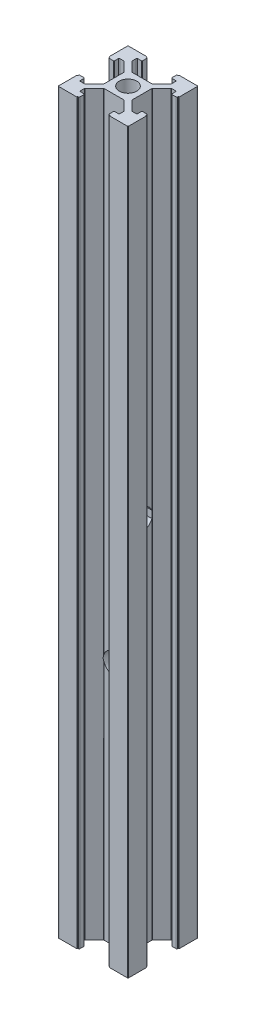
SolidWorks part; units mm, degrees
material "6063-O"
ref_plane "Ön Düzlem" through (0, 0, 0) normal (0, 0, 1) x (1, 0, 0)
ref_plane "Üst Düzlem" through (0, 0, 0) normal (0, 1, 0) x (1, 0, 0)
ref_plane "Sağ Düzlem" through (0, 0, 0) normal (1, 0, 0) x (0, 0, -1)
sketch "Sketch1" plane through (0, 0, 0) normal (0, 1, 0) x (1, 0, 0)
  line L0 (-10, 4.65) -> (-9.8, 4.65)
  line L1 (-9.8, -10) -> (-4.65, -10)
  line L2 (-10, -9.8) -> (-10, -4.65)
  line L3 (-9.8, 10) -> (-4.65, 10)
  line L4 (10, -9.8) -> (10, -4.65)
  line L5 (-10, -10) -> (10, 10) construction
  line L6 (-10, 10) -> (10, -10) construction
  line L7 (-9.8, 4.65) -> (-9.8, 4.4)
  line L8 (-9.6, 4.2) -> (-8.4, 4.2)
  line L9 (-4, 2.8172) -> (-4, -2.8172)
  line L10 (-8.2, 4.4) -> (-8.2, 5.45)
  line L11 (-8, 5.65) -> (-6.8328, 5.65)
  line L12 (-6.6914, 5.5914) -> (-4.0586, 2.9586)
  line L13 (-9.8, -4.65) -> (-10, -4.65)
  line L14 (-6.6914, -5.5914) -> (-4.0586, -2.9586)
  line L15 (-8, -5.65) -> (-6.8328, -5.65)
  line L16 (-8.2, -4.4) -> (-8.2, -5.45)
  line L17 (-9.6, -4.2) -> (-8.4, -4.2)
  line L18 (-9.8, -4.65) -> (-9.8, -4.4)
  line L19 (4.65, 10) -> (4.65, 9.8)
  line L20 (-10, 4.65) -> (-10, 9.8)
  line L21 (4.65, 9.8) -> (4.4, 9.8)
  line L22 (4.2, 9.6) -> (4.2, 8.4)
  line L23 (4.4, 8.2) -> (5.45, 8.2)
  line L24 (5.65, 8) -> (5.65, 6.8328)
  line L25 (5.5914, 6.6914) -> (2.9586, 4.0586)
  line L26 (2.8172, 4) -> (-2.8172, 4)
  line L27 (-5.5914, 6.6914) -> (-2.9586, 4.0586)
  line L28 (-5.65, 8) -> (-5.65, 6.8328)
  line L29 (-4.4, 8.2) -> (-5.45, 8.2)
  line L30 (-4.2, 9.6) -> (-4.2, 8.4)
  line L31 (-4.65, 9.8) -> (-4.4, 9.8)
  line L32 (-4.65, 9.8) -> (-4.65, 10)
  line L33 (10, -4.65) -> (9.8, -4.65)
  line L34 (9.8, -4.65) -> (9.8, -4.4)
  line L35 (9.6, -4.2) -> (8.4, -4.2)
  line L36 (8.2, -4.4) -> (8.2, -5.45)
  line L37 (8, -5.65) -> (6.8328, -5.65)
  line L38 (6.6914, -5.5914) -> (4.0586, -2.9586)
  line L39 (4, -2.8172) -> (4, 2.8172)
  line L40 (6.6914, 5.5914) -> (4.0586, 2.9586)
  line L41 (8, 5.65) -> (6.8328, 5.65)
  line L42 (8.2, 4.4) -> (8.2, 5.45)
  line L43 (9.6, 4.2) -> (8.4, 4.2)
  line L44 (9.8, 4.65) -> (9.8, 4.4)
  line L45 (9.8, 4.65) -> (10, 4.65)
  line L46 (-4.65, -10) -> (-4.65, -9.8)
  line L47 (-4.65, -9.8) -> (-4.4, -9.8)
  line L48 (-4.2, -9.6) -> (-4.2, -8.4)
  line L49 (-4.4, -8.2) -> (-5.45, -8.2)
  line L50 (-5.65, -8) -> (-5.65, -6.8328)
  line L51 (-5.5914, -6.6914) -> (-2.9586, -4.0586)
  line L52 (-2.8172, -4) -> (2.8172, -4)
  line L53 (5.5914, -6.6914) -> (2.9586, -4.0586)
  line L54 (5.65, -8) -> (5.65, -6.8328)
  line L55 (4.4, -8.2) -> (5.45, -8.2)
  line L56 (4.2, -9.6) -> (4.2, -8.4)
  line L57 (4.65, -9.8) -> (4.4, -9.8)
  line L58 (4.65, -9.8) -> (4.65, -10)
  line L59 (4.65, -10) -> (9.8, -10)
  line L60 (10, 4.65) -> (10, 9.8)
  line L61 (4.65, 10) -> (9.8, 10)
  arc A0 (-9.8, 4.4) -> (-9.6, 4.2) centre (-9.6, 4.4) ccw
  arc A1 (-9.8, -4.4) -> (-9.6, -4.2) centre (-9.6, -4.4) cw
  arc A2 (-8.4, 4.2) -> (-8.2, 4.4) centre (-8.4, 4.4) ccw
  arc A3 (-8.2, 5.45) -> (-8, 5.65) centre (-8, 5.45) cw
  arc A4 (-6.6914, 5.5914) -> (-6.8328, 5.65) centre (-6.8328, 5.45) ccw
  arc A5 (-4, 2.8172) -> (-4.0586, 2.9586) centre (-4.2, 2.8172) ccw
  arc A6 (-6.6914, -5.5914) -> (-6.8328, -5.65) centre (-6.8328, -5.45) cw
  arc A7 (-4, -2.8172) -> (-4.0586, -2.9586) centre (-4.2, -2.8172) cw
  arc A8 (-8, -5.65) -> (-8.2, -5.45) centre (-8, -5.45) cw
  arc A9 (-8.2, -4.4) -> (-8.4, -4.2) centre (-8.4, -4.4) ccw
  arc A10 (4.4, 9.8) -> (4.2, 9.6) centre (4.4, 9.6) ccw
  arc A11 (4.2, 8.4) -> (4.4, 8.2) centre (4.4, 8.4) ccw
  arc A12 (5.45, 8.2) -> (5.65, 8) centre (5.45, 8) cw
  arc A13 (5.5914, 6.6914) -> (5.65, 6.8328) centre (5.45, 6.8328) ccw
  arc A14 (2.8172, 4) -> (2.9586, 4.0586) centre (2.8172, 4.2) ccw
  arc A15 (-2.8172, 4) -> (-2.9586, 4.0586) centre (-2.8172, 4.2) cw
  arc A16 (-5.5914, 6.6914) -> (-5.65, 6.8328) centre (-5.45, 6.8328) cw
  arc A17 (-5.65, 8) -> (-5.45, 8.2) centre (-5.45, 8) cw
  arc A18 (-4.4, 8.2) -> (-4.2, 8.4) centre (-4.4, 8.4) ccw
  arc A19 (-4.4, 9.8) -> (-4.2, 9.6) centre (-4.4, 9.6) cw
  arc A20 (9.8, -4.4) -> (9.6, -4.2) centre (9.6, -4.4) ccw
  arc A21 (8.4, -4.2) -> (8.2, -4.4) centre (8.4, -4.4) ccw
  arc A22 (8.2, -5.45) -> (8, -5.65) centre (8, -5.45) cw
  arc A23 (6.6914, -5.5914) -> (6.8328, -5.65) centre (6.8328, -5.45) ccw
  arc A24 (4, -2.8172) -> (4.0586, -2.9586) centre (4.2, -2.8172) ccw
  arc A25 (4, 2.8172) -> (4.0586, 2.9586) centre (4.2, 2.8172) cw
  arc A26 (6.6914, 5.5914) -> (6.8328, 5.65) centre (6.8328, 5.45) cw
  arc A27 (8, 5.65) -> (8.2, 5.45) centre (8, 5.45) cw
  arc A28 (8.2, 4.4) -> (8.4, 4.2) centre (8.4, 4.4) ccw
  arc A29 (9.8, 4.4) -> (9.6, 4.2) centre (9.6, 4.4) cw
  arc A30 (-4.4, -9.8) -> (-4.2, -9.6) centre (-4.4, -9.6) ccw
  arc A31 (-4.2, -8.4) -> (-4.4, -8.2) centre (-4.4, -8.4) ccw
  arc A32 (-5.45, -8.2) -> (-5.65, -8) centre (-5.45, -8) cw
  arc A33 (-5.5914, -6.6914) -> (-5.65, -6.8328) centre (-5.45, -6.8328) ccw
  arc A34 (-2.8172, -4) -> (-2.9586, -4.0586) centre (-2.8172, -4.2) ccw
  arc A35 (2.8172, -4) -> (2.9586, -4.0586) centre (2.8172, -4.2) cw
  arc A36 (5.5914, -6.6914) -> (5.65, -6.8328) centre (5.45, -6.8328) cw
  arc A37 (5.65, -8) -> (5.45, -8.2) centre (5.45, -8) cw
  arc A38 (4.4, -8.2) -> (4.2, -8.4) centre (4.4, -8.4) ccw
  arc A39 (4.4, -9.8) -> (4.2, -9.6) centre (4.4, -9.6) cw
  arc A40 (-9.8, -10) -> (-10, -9.8) centre (-9.8, -9.8) cw
  arc A41 (9.8, -10) -> (10, -9.8) centre (9.8, -9.8) ccw
  arc A42 (10, 9.8) -> (9.8, 10) centre (9.8, 9.8) ccw
  arc A43 (-10, 9.8) -> (-9.8, 10) centre (-9.8, 9.8) cw
  circle A44 centre (0, 0) radius 2.5
  point P0 (0, 0)
  point P12 (-9.8, 4.2)
  point P27 (-9.8, -4.2)
  point P30 (-8.2, 4.2)
  point P33 (-8.2, 5.65)
  point P36 (-6.75, 5.65)
  point P39 (-4, 2.9)
  point P42 (-6.75, -5.65)
  point P45 (-4, -2.9)
  point P48 (-8.2, -5.65)
  point P51 (-8.2, -4.2)
  dimension "D11" = 0.2
  dimension "D13" = 0.2
  dimension "D14" = 5
  dimension "D1" = 20
  dimension "D2" = 20
  dimension "D3" = 5.35
  dimension "D4" = 0.2
  dimension "D5" = 0.45
  dimension "D6" = 1.6
  dimension "D7" = 4.2
  dimension "D8" = 1.45
  dimension "D9" = 1.45
  dimension "D10" = 135
  dimension "D12" = 4
extrude "Boss-Extrude1" add sketch "Sketch1" along normal blind 211
sketch "Sketch2" plane through (4, 0, 0) normal (1, 0, 0) x (0, 0, -1)
  line L0 (0, 211) -> (0, 0)
  line L1 (-2.8172, 211) -> (2.8172, 211) construction
  circle A0 centre (0, 105.5) radius 3
  line M2 (2.8172, 0) -> (2.8172, 211)
  line M4 (-2.8172, 211) -> (-2.8172, 0)
extrude "Cut-Extrude1" cut sketch "Sketch2" against normal blind 10 and the other way blind 10 contours A0 L0 M2 | L0 A0 M4 region at (4, 105.5, -1.2438) region at (4, 105.5, 1.2438)
sketch "Sketch3" plane through (0, 0, 10) normal (0, 0, 1) x (1, 0, 0)
  line L0 (0, 211) -> (0, 0)
  line L1 (-2.8172, 211) -> (2.8172, 211) construction
sketch "Sketch4" plane through (0, 0, 4) normal (0, 0, 1) x (1, 0, 0)
  circle A0 centre (0, 69.881) radius 3
extrude "Cut-Extrude2" cut sketch "Sketch4" against normal blind 10 and the other way blind 10
